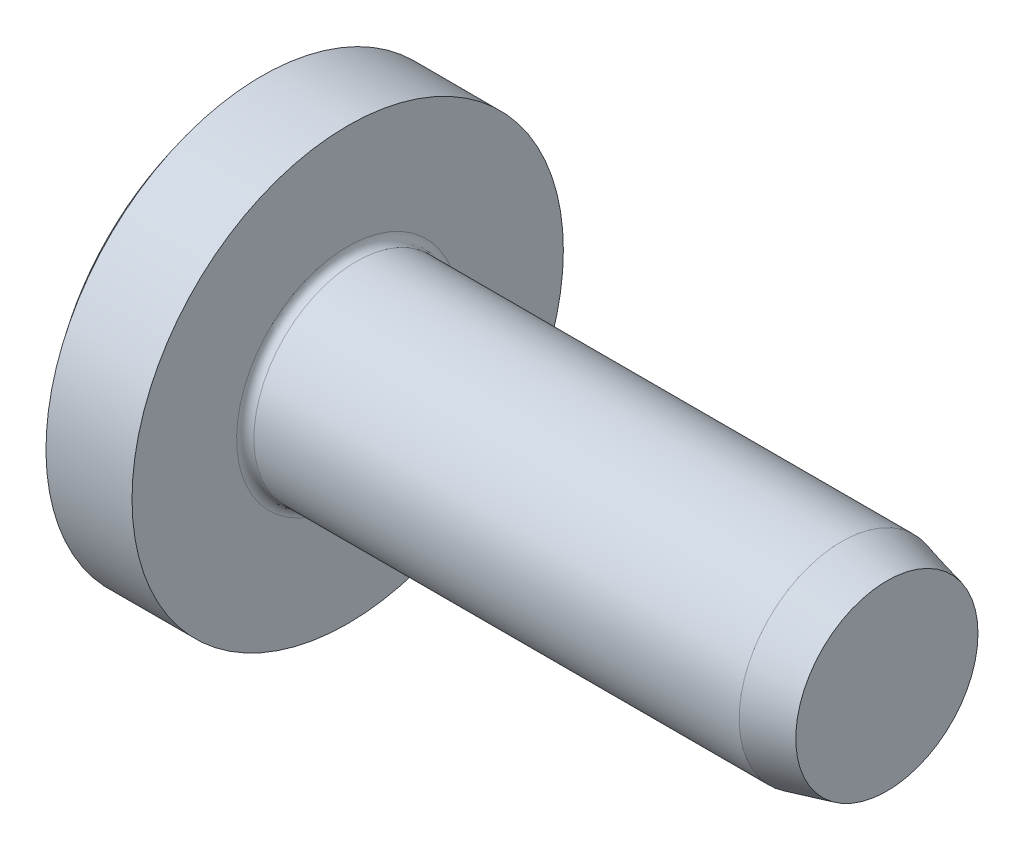
SolidWorks part; units mm, degrees
ref_plane "Front" through (0, 0, 0) normal (0, 0, 1) x (1, 0, 0)
ref_plane "Top" through (0, 0, 0) normal (0, 1, 0) x (1, 0, 0)
ref_plane "Right" through (0, 0, 0) normal (1, 0, 0) x (0, 0, -1)
sketch "Sketch1" plane through (0, 0, 0) normal (0, 0, 1) x (1, 0, 0)
  line L0 (-65.5475, 0) -> (9.6, 0) construction
  line L1 (32.5, 0) -> (32.5, 4.75)
  line L2 (32.5, 4.75) -> (7.5, 4.75)
  line L3 (7.5, 4.75) -> (7.5, 10)
  line L4 (7.5, 10) -> (3.51, 10)
  line L5 (32.5, 0) -> (0, 0)
  arc A0 (3.51, 10) -> (0, 0) centre (16, 0) ccw
  dimension "l" = 25
revolve "Base" add sketch "Sketch1" angle 360 about L0
cosmetic thread "ThreadCosmetic1" [suppressed] parameters "D1"=25, "D2"=8.5
sketch "Sketch2" plane through (0, 0, 0) normal (1, 0, 0) x (0, 0, -1)
  line L0 (6.5369, 0) -> (-7.0008, 0) construction
  line L1 (0, 6.811) -> (0, -6.4314) construction
  line L2 (-1.01, 5.05) -> (1.01, 5.05)
  line L3 (1.01, 5.05) -> (1.01, 1.01)
  line L4 (1.01, 1.01) -> (5.05, 1.01)
  line L5 (5.05, 1.01) -> (5.05, -1.01)
  line L6 (1.01, -1.01) -> (5.05, -1.01)
  line L7 (1.01, -5.05) -> (1.01, -1.01)
  line L8 (-1.01, -5.05) -> (1.01, -5.05)
  line L9 (-1.01, -5.05) -> (-1.01, -1.01)
  line L10 (-1.01, -1.01) -> (-5.05, -1.01)
  line L11 (-5.05, 1.01) -> (-5.05, -1.01)
  line L12 (-1.01, 1.01) -> (-5.05, 1.01)
  line L13 (-1.01, 5.05) -> (-1.01, 1.01)
  point P5 (-5.05, 0)
  point P11 (5.05, 0)
  point P15 (0, -5.05)
  point P20 (0, 5.05)
  dimension "D2" = 10.1
  dimension "D3" = 2.02
  dimension "D4" = 2.02
extrude "CrossRecess" cut sketch "Sketch2" along normal blind 5.2
fillet "Fillet1" radius 0.4 1 edges at (7.5, -4.75, 0)
sketch "Sketch3" plane through (0, 0, 0) normal (1, 0, 0) x (0, 0, -1)
  line L0 (-4.5467, 4.5467) -> (4.5467, -4.5467) construction
  line L1 (-4.379, 4.379) -> (-1.01, 2.02)
  line L3 (-1.01, 2.02) -> (-1.01, 1.01)
  line L4 (-2.02, 1.01) -> (-1.01, 1.01)
  line L5 (-4.379, 4.379) -> (-2.02, 1.01)
  line L6 (7.069, 0) -> (-6.5067, 0) construction
  line L7 (0, 5.9645) -> (0, -0.3816) construction
  line L8 (4.379, 4.379) -> (2.02, 1.01)
  line L9 (2.02, 1.01) -> (1.01, 1.01)
  line L10 (1.01, 2.02) -> (1.01, 1.01)
  line L11 (4.379, 4.379) -> (1.01, 2.02)
  line L12 (4.379, -4.379) -> (1.01, -2.02)
  line L13 (1.01, -2.02) -> (1.01, -1.01)
  line L14 (2.02, -1.01) -> (1.01, -1.01)
  line L15 (4.379, -4.379) -> (2.02, -1.01)
  line L16 (-4.379, -4.379) -> (-2.02, -1.01)
  line L17 (-2.02, -1.01) -> (-1.01, -1.01)
  line L18 (-1.01, -2.02) -> (-1.01, -1.01)
  line L19 (-4.379, -4.379) -> (-1.01, -2.02)
  line L21 (1.01, 5.05) -> (1.01, 1.01) construction
  line L22 (1.01, 1.01) -> (5.05, 1.01) construction
  dimension "D1" = 20
  dimension "D2" = 1.01
extrude "Cut-Extrude2" [suppressed] cut sketch "Sketch3" along normal up to surface (5.2 mm away) up to face at (5.2, 0, 0)
sketch "Sketch4" plane through (0, 0, 0) normal (0, 0, 1) x (1, 0, 0)
  line L0 (1.3282, 0) -> (-13.6388, 0) construction
  line L1 (7.9, -4.75) -> (32.5, -4.75) construction
  line L2 (28.3, -4.75) -> (30.4, -4.75)
  line L3 (30.4, -4.75) -> (32.5, -4.225)
  line L6 (28.3, -4.75) -> (28.3, -5.25)
  line L7 (28.3, -5.25) -> (32.5, -5.25)
  line L8 (32.5, -5.25) -> (32.5, -4.225)
  line L9 (32.5, -4.75) -> (32.5, 4.75) construction
  point P15 (30.4, -4.75)
  dimension "D2" = 2.1
  dimension "D4" = 0.5
  dimension "D3" = 0.525
revolve "Cut-Revolve1" cut sketch "Sketch4" angle 360 about L0
sketch "Sketch5" plane through (0, 0, 0) normal (0, 0, 1) x (1, 0, 0)
  line L0 (35.2407, 0) -> (11.9121, 0) construction
  line L2 (32.5, -4.75) -> (32.5, 4.75) construction
  line L3 (32.5, 0) -> (24.5, -4.75) construction
  line L6 (32.5, 0) -> (33, 0)
  line L7 (24.5, -4.75) -> (32.5, -4.75)
  line L8 (33, 0) -> (33, -4.75)
  line L9 (33, -4.75) -> (32.5, -4.75)
  arc A0 (32.5, 0) -> (24.5, -4.75) centre (12.3363, 24.8481) cw
  dimension "D1" = 32
  dimension "D3" = 9.5
  dimension "D2" = 0.5
revolve "Cut-Revolve6" [suppressed] cut sketch "Sketch5" angle 360 about L0
draft "Draft1" type of draft neutral plane draft angle 30 neutral plane "Right" faces to draft 4 face at (3.0173, -5.05, 0) face at (3.0173, 0, 5.05) face at (3.0173, 5.05, 0) face at (3.0173, 0, -5.05) neutral plane through (0, 0, 0) neutral plane normal (1, 0, 0) reverse direction yes parameters "D1"=30
sketch "Sketch6" plane through (0, 0, 0) normal (0, 0, 1) x (1, 0, 0)
  line L0 (7.9, 5.25) -> (7.9, 4.75)
  line L1 (7.9, 4.75) -> (8.15, 4.317)
  line L2 (8.15, 4.317) -> (8.4, 4.75)
  line L3 (8.4, 4.75) -> (8.4, 5.25)
  line L4 (8.4, 5.25) -> (7.9, 5.25)
  line L5 (0, 0) -> (34.661, 0) construction
  line L7 (7.9, -4.75) -> (7.9, 4.75) construction
  dimension "D2" = 9.5
  dimension "D1" = 0.5
revolve "Cut-Revolve10" [suppressed] cut sketch "Sketch6" angle 360 about L5
pattern_linear "LPattern10" [suppressed] count 41 along (1, 0, 0) of bodies 106
equation "\"D3@Sketch2\" = \"m@Sketch2\" / 5"
equation "\"D4@Sketch2\" = \"D3@Sketch2\""
equation "\"D2@Sketch2\" = \"m@Sketch2\""
equation "\"D2@Sketch3\" = \"m@Sketch2\" / 10"
equation "\"D3@Sketch4\" = \"yf@Sketch4\" / 8"
equation "\"D2@ThreadCosmetic1\" = \"st@Sketch1\" - 1"
equation "\"D1@Sketch5\" = \"yc@Sketch5\" * 4"
equation "\"D3@Sketch5\" = \"st@Sketch1\""
equation "\"D2@Sketch4\" = \"yf@Sketch4\" / 2"
equation "\"D2@Sketch6\" = \"st@Sketch1\""
equation "\"D1@ThreadCosmetic1\" = \"l@Sketch1\" "
equation "\"D1@Sketch6\" = (  \"D2@Sketch6\" - \"D2@ThreadCosmetic1\" )  / 2"
equation "\"pitch@LPattern10\" = \"D1@Sketch6\" * 1.2"
equation "\"D1@LPattern10\" = \"D1@ThreadCosmetic1\" / \"pitch@LPattern10\" - 1"
